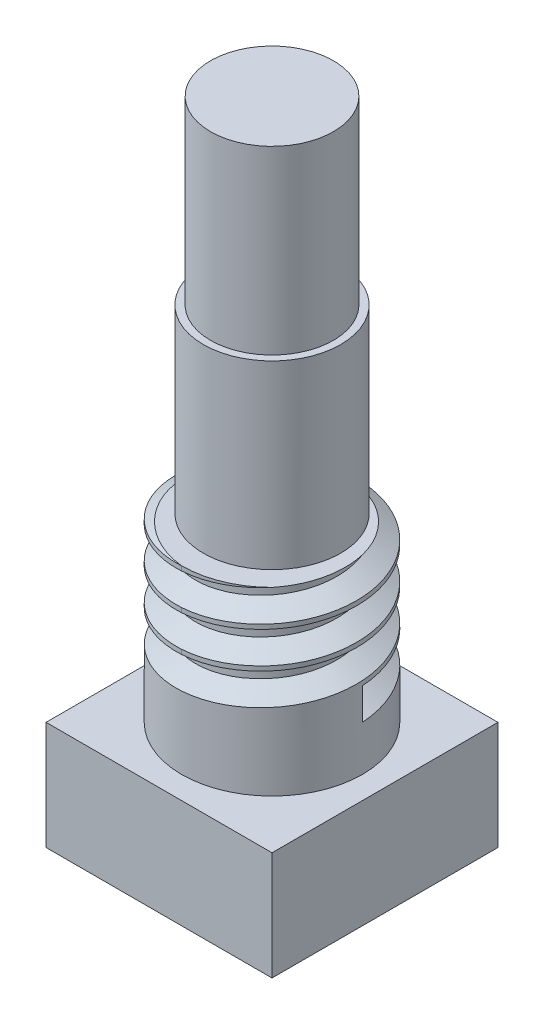
SolidWorks part; units mm, degrees
ref_plane "Front Plane" through (0, 0, 0) normal (0, 0, 1) x (1, 0, 0)
ref_plane "Top Plane" through (0, 0, 0) normal (0, 1, 0) x (1, 0, 0)
ref_plane "Right Plane" through (0, 0, 0) normal (1, 0, 0) x (0, 0, -1)
sketch "Sketch1" plane through (0, 0, 0) normal (0, 1, 0) x (1, 0, 0)
  circle A0 centre (0, 0) radius 2.413
  dimension "D1" = 4.826
extrude "Boss-Extrude1" add sketch "Sketch1" along normal blind 6.35
sketch "Sketch2" plane through (0, 0, 0) normal (0, -1, 0) x (-1, 0, 0)
  circle A0 centre (0, 0) radius 2.413
  dimension "D1" = 4.826
extrude "Boss-Extrude2" add sketch "Sketch2" along normal blind 4.7622
sketch "Sketch3" plane through (0, -4.7622, 0) normal (0, -1, 0) x (-1, 0, 0)
  circle A0 centre (0, 0) radius 3.175
  dimension "D1" = 6.35
extrude "Boss-Extrude3" add sketch "Sketch3" along normal blind 3.175
sketch "Sketch4" plane through (0, -7.9372, 0) normal (0, -1, 0) x (-1, 0, 0)
  circle A0 centre (0, 0) radius 3.175
  dimension "D1" = 6.35
extrude "Boss-Extrude4" add sketch "Sketch4" along normal blind 3.175
thread "Thread2" pitch 1.27 method cut profile "Thread Profile3" start angle 0, offset 1.5875, length 0, pitch 1.27, diameter 6.35
ref_plane "Plane3" through (3.175, -9.5247, 0) normal (0, 0, 1) x (1, 0, 0)
sketch "Thread Profile3" plane through (3.175, -9.5247, 0) normal (0, 0, 1) x (1, 0, 0)
  line L0 (0, 0) -> (0, 1.27) construction
  line L11 (0, 0) -> (0, 1.1112)
  line L12 (0, 1.1112) -> (-0.6874, 0.7144)
  line L13 (-0.6874, 0.7144) -> (-0.6874, 0.3969)
  line L15 (-0.6874, 0.3969) -> (0, 0)
  line L17 (-0.6874, 0.5556) -> (0, 0.5556) construction
  point P2 (0, 0)
  dimension "Pitch" = 1.27
  dimension "Profile_Angle" = 60
  dimension "Profile_Land" = 0.3175
  dimension "Profile_Height" = 0.6874
sketch "Sketch11" plane through (0, -11.1122, 0) normal (0, -1, 0) x (-1, 0, 0)
  circle A0 centre (0, 0) radius 6.35
  dimension "D1" = 12.7
extrude "Boss-Extrude5" add sketch "Sketch11" along normal blind 3.81
fillet "Fillet1" [suppressed] radius 2.54
sketch "Sketch13" plane through (0, 6.35, 0) normal (0, 1, 0) x (1, 0, 0)
  circle A0 centre (0, 0) radius 2.413
extrude "Cut-Extrude1" cut sketch "Sketch13" against normal blind 0.9522
sketch "Sketch14" plane through (0, 5.3978, 0) normal (0, 1, 0) x (1, 0, 0)
  circle A0 centre (0, 0) radius 2.413
extrude "Boss-Extrude6" add sketch "Sketch14" along normal blind 2.54
sketch "Sketch15" plane through (0, -14.9222, 0) normal (0, -1, 0) x (1, 0, 0)
  line L1 (3.9687, 3.9687) -> (-3.9688, 3.9687)
  line L2 (3.9687, 3.9687) -> (3.9688, -3.9688)
  line L3 (3.9688, -3.9688) -> (-3.9688, -3.9688)
  line L4 (-3.9688, 3.9687) -> (-3.9688, -3.9688)
  line L5 (3.9687, 3.9687) -> (-3.9688, -3.9688) construction
  line L6 (3.9688, -3.9688) -> (-3.9688, 3.9687) construction
  point P0 (0, 0)
  dimension "D1" = 7.9375
  dimension "D2" = 7.9375
sketch "Sketch16" plane through (0, -14.9222, 0) normal (0, -1, 0) x (1, 0, 0)
  line L1 (3.9687, 3.9687) -> (-7.1421, 3.9687)
  line L2 (3.9687, 3.9687) -> (3.9687, 7.0567)
  line L3 (3.9687, 7.0567) -> (-7.1421, 7.0567)
  line L4 (-7.1421, 3.9687) -> (-7.1421, 7.0567)
  line L5 (-3.9688, 3.9687) -> (-7.1421, 3.9687)
  line L6 (-3.9688, 3.9687) -> (-3.9688, -6.8081)
  line L7 (-3.9688, -6.8081) -> (-7.1421, -6.8081)
  line L8 (-7.1421, 3.9687) -> (-7.1421, -6.8081)
  line L9 (-3.9688, -3.9688) -> (6.6445, -3.9688)
  line L10 (-3.9688, -3.9688) -> (-3.9688, -6.8081)
  line L11 (-3.9688, -6.8081) -> (6.6445, -6.8081)
  line L12 (6.6445, -3.9688) -> (6.6445, -6.8081)
  line L13 (3.9688, -3.9688) -> (6.6445, -3.9688)
  line L14 (3.9688, -3.9688) -> (3.9687, 7.0567)
  line L15 (3.9687, 7.0567) -> (6.6445, 7.0567)
  line L16 (6.6445, -3.9688) -> (6.6445, 7.0567)
  circle M9 centre (0, 0) radius 6.35
extrude "Cut-Extrude3" cut sketch "Sketch16" against normal blind 3.81 contours L9 L16 L15 L2 M9 | L4 L1 L2 L3 M9 | L1 L8 L7 L6 M9 | L6 L1 M9 | L1 L2 M9 | L14 L9 L2 M9 | L9 L6 M9 | L12 L9 L6 L11 M9 region at (-0.1419, -14.9222, 4.9591) region at (4.9591, -14.9222, 0.1419) region at (-4.9591, -14.9222, -0.1419) region at (-2.8371, -14.9222, 5.9919) region at (5.7139, -14.9222, 3.187) region at (0.1419, -14.9222, -4.9591) region at (-6.0747, -14.9222, -2.5323) region at (2.677, -14.9222, -5.8691)
sketch "Sketch17" plane through (0, 7.9378, 0) normal (0, 1, 0) x (1, 0, 0)
  circle A0 centre (0, 0) radius 2.159
  circle A1 centre (0, 0) radius 2.413
extrude "Cut-Extrude4" cut sketch "Sketch17" against normal blind 6.35
